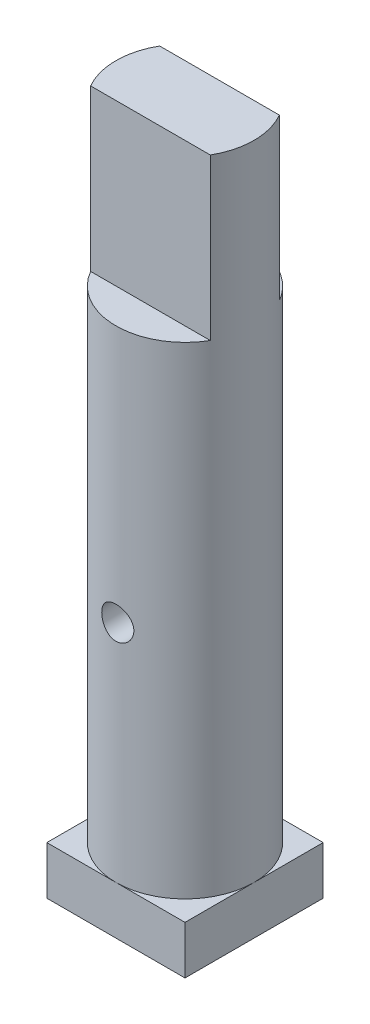
SolidWorks part; units mm, degrees
ref_plane "Front Plane" through (0, 0, 0) normal (0, 0, 1) x (1, 0, 0)
ref_plane "Top Plane" through (0, 0, 0) normal (0, 1, 0) x (1, 0, 0)
ref_plane "Right Plane" through (0, 0, 0) normal (1, 0, 0) x (0, 0, -1)
sketch "Sketch1" plane through (0, 0, 0) normal (0, 1, 0) x (1, 0, 0)
  line L0 (-4.3, 4.3) -> (4.3, 4.3)
  line L1 (-4.5, -4.5) -> (4.5, -4.5) construction
  line L2 (-4.5, -4.5) -> (-4.5, 4.5) construction
  line L3 (-4.5, 4.5) -> (4.5, 4.5) construction
  line L4 (4.5, -4.5) -> (4.5, 4.5) construction
  line L5 (4.3, -4.3) -> (4.3, 4.3)
  line L6 (-4.3, -4.3) -> (4.3, -4.3)
  line L7 (-4.3, -4.3) -> (-4.3, 4.3)
  point P0 (0, 0)
  dimension "D1" = 9
  dimension "D2" = 9
  dimension "D3" = 0.2
extrude "Boss-Extrude1" add sketch "Sketch1" along normal blind 3
sketch "Sketch2" plane through (0, 3, 0) normal (0, 1, 0) x (1, 0, 0)
  line L0 (-4.3, 4.3) -> (4.3, -4.3) construction
  line L1 (4.3, 4.3) -> (-4.3, -4.3) construction
  circle A0 centre (0, 0) radius 4.3
extrude "Boss-Extrude2" add sketch "Sketch2" along normal blind 40
sketch "Sketch3" plane through (0, 3, 0) normal (0, 1, 0) x (1, 0, 0)
  circle A0 centre (0, 0) radius 1.6
  circle A1 centre (0, 0) radius 2
extrude "Cut-Extrude1" cut sketch "Sketch3" along normal blind 3 from offset 7.6
sketch "Sketch4" plane through (0, 43, 0) normal (0, 1, 0) x (1, 0, 0)
  line L0 (0, 4.3) -> (0, 0) construction
  line L1 (-4.3, 0) -> (4.3, 0) construction
  line L2 (0, 2.15) -> (-3.7239, 2.15)
  line L3 (0, 2.15) -> (3.7239, 2.15)
  line L4 (0, -2.15) -> (-3.7239, -2.15)
  line L5 (0, -2.15) -> (3.7239, -2.15)
  circle A0 centre (0, 0) radius 4.3 construction
  circle A1 centre (0, 0) radius 4.3 construction
  arc A2 (-3.7239, 2.15) -> (3.7239, 2.15) centre (0, 0) cw
  arc A3 (-3.7239, -2.15) -> (3.7239, -2.15) centre (0, 0) ccw
extrude "Cut-Extrude2" cut sketch "Sketch4" against normal blind 10
fillet "Fillet1" radius 1 2 edges at (0, 13.6, 1.6) (0, 10.6, 1.6)
sketch "Sketch5" plane through (0, 43, 0) normal (0, 1, 0) x (1, 0, 0)
  line L2 (-3.7239, -2.15) -> (3.7239, -2.15)
  line L3 (3.7239, 2.15) -> (-3.7239, 2.15)
  line L4 (-3.7239, -2.15) -> (3.7239, -2.15)
  line L5 (3.7239, 2.15) -> (-3.7239, 2.15)
  arc A2 (3.7239, -2.15) -> (3.7239, 2.15) centre (0, 0) ccw
  arc A3 (-3.7239, 2.15) -> (-3.7239, -2.15) centre (0, 0) ccw
  arc A4 (3.7239, -2.15) -> (3.7239, 2.15) centre (0, 0) ccw
  arc A5 (-3.7239, 2.15) -> (-3.7239, -2.15) centre (0, 0) ccw
  dimension "D1" = 0
sketch "Sketch7" plane through (0, 0, -4.3) normal (0, 0, -1) x (-1, 0, 0)
  line L0 (0, 0) -> (0, 17) construction
  circle A0 centre (0, 17) radius 1
extrude "Cut-Extrude3" cut sketch "Sketch7" against normal blind 10
